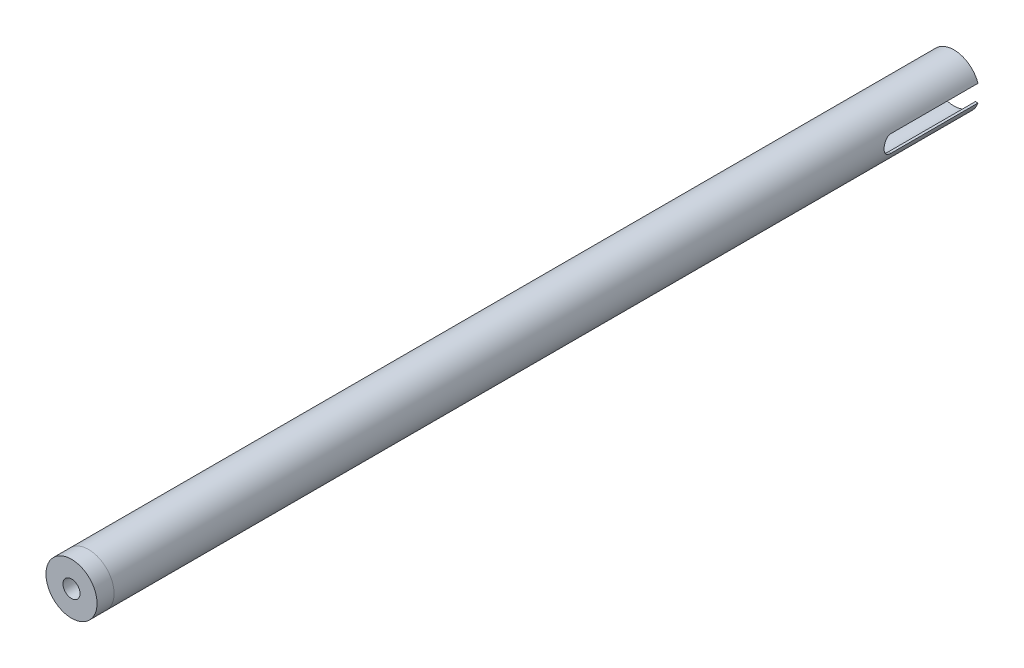
SolidWorks part; units mm, degrees
material "AISI 4130 Steel, annealed at 865C"
ref_plane "Front Plane" through (0, 0, 0) normal (0, 0, 1) x (1, 0, 0)
ref_plane "Top Plane" through (0, 0, 0) normal (0, 1, 0) x (1, 0, 0)
ref_plane "Right Plane" through (0, 0, 0) normal (1, 0, 0) x (0, 0, -1)
sketch "Axis" plane through (0, 0, 0) normal (0, 1, 0) x (1, 0, 0)
  line L0 (0, 0) -> (0, 329.0571) construction
  line L1 (0, 0) -> (0, -21.9075) construction
  line L2 (0, 329.0571) -> (-9.525, 329.0571) construction
  line L4 (0, 363.141) -> (-23.5893, 278.7301) construction
  dimension "D1" = 21.9075
  dimension "D2" = 9.525
sketch "Sketch1" plane through (0, 0, 0) normal (0, 0, 1) x (1, 0, 0)
  line L0 (-9.525, 0) -> (9.525, 0) construction
  line L1 (-8.9803, 3.175) -> (8.9803, 3.175)
  line L2 (-8.9803, -3.175) -> (8.9803, -3.175)
  circle A0 centre (0, 0) radius 9.525
  circle A1 centre (0, 0) radius 8.636
  circle A2 centre (0, 0) radius 3.175
  dimension "D1" = 19.05
  dimension "D3" = 6.35
  dimension "D2" = 0.889
  dimension "D4" = 6.35
extrude "Threaded insert 1-1" add sketch "Sketch1" against normal blind 6.35 contours A2 L1 A1 | A1 L1 A0 | A2 L0 A1 L1 | A1 L0 A0 L1 | L0 A1 L2 A0 | L0 A2 L2 A1 | A2 L2 A1 | A1 L2 A0 | L0 A1 L2 A2 | L0 A0 L2 A1 | A0 L0 A1 L1 | A1 L0 A2 L1 region at (5.4259, 1.6615, 0) region at (5.4259, -1.6615, 0) region at (8.8881, 1.6046, 0) region at (8.8881, -1.6046, 0) region at (-5.4259, -1.6615, 0) region at (-5.4259, 1.6615, 0) region at (0, 5.4321, 0) region at (0, -5.4321, 0) region at (0, 8.8265, 0) region at (8.5057, -3.3655, 0) region at (-8.8881, -1.6046, 0) region at (-8.8881, 1.6046, 0)
extrude "Threaded insert 1-2" add sketch "Sketch1<3>" against normal blind 6.35 from surface contours A2 L1 A1 | A2 L0 A1 L1 | L0 A2 L2 A1 | A2 L2 A1 | L0 A1 L2 A2 | A1 L0 A2 L1 region at (5.4259, 1.6615, 0) region at (5.4259, -1.6615, 0) region at (-5.4259, -1.6615, 0) region at (-5.4259, 1.6615, 0) region at (0, 5.4321, 0) region at (0, -5.4321, 0) starting at face at (9.525, 0, -6.35)
sketch "Sketch1<3>" plane through (0, 0, 0) normal (0, 0, 1) x (1, 0, 0) same geometry as "Sketch1"
extrude "A-arm tube" add sketch "Sketch1<4>" against normal up to vertex (329.0571 mm away) from surface separate body contours A1 L1 A0 | A1 L0 A0 L1 | L0 A1 L2 A0 | A1 L2 A0 | L0 A0 L2 A1 | A0 L0 A1 L1 region at (8.8881, 1.6046, 0) region at (8.8881, -1.6046, 0) region at (0, 8.8265, 0) region at (8.5057, -3.3655, 0) region at (-8.8881, -1.6046, 0) region at (-8.8881, 1.6046, 0) up to point (0, 0, -329.0571) starting at face at (8.636, 0, -6.35)
sketch "Sketch1<4>" plane through (0, 0, 0) normal (0, 0, 1) x (1, 0, 0) same geometry as "Sketch1"
extrude "Apex slot" cut sketch "Sketch1<5>" along normal blind 35.56 from surface contours A0 L0 A1 L1 | L0 A0 L2 A1 | A1 L0 A0 L1 | L0 A1 L2 A0 region at (8.8881, 1.6046, 0) region at (8.8881, -1.6046, 0) region at (-8.8881, -1.6046, 0) region at (-8.8881, 1.6046, 0) starting at face at (8.636, 0, -329.0571)
sketch "Sketch1<5>" plane through (0, 0, 0) normal (0, 0, 1) x (1, 0, 0) same geometry as "Sketch1"
fillet "Fillet1" radius 3.175 4 edges at (-8.5057, 3.175, -293.4971) (-8.5057, -3.175, -293.4971) (8.5057, -3.175, -293.4971) (8.5057, 3.175, -293.4971)
equation "\"tube diameter\"= 3 / 4"
equation "\"tube thickness\"= .035"
equation "\"apex thickness\"= .25"
equation "\"tube slot\"= 1.4"
equation "\"D1@Sketch1\"=\"tube diameter\""
equation "\"D2@Sketch1\"=\"tube thickness\""
equation "\"threaded insert hole\"= 1 / 4"
equation "\"D3@Sketch1\"=\"threaded insert hole\""
equation "\"D4@Sketch1\"=\"apex thickness\""
equation "\"D1@Apex slot\" = \"tube slot\""
equation "\"D1@Fillet1\"=\"apex thickness\"/2"
equation "\"D2@Axis\"=\"tube diameter\"/2"
